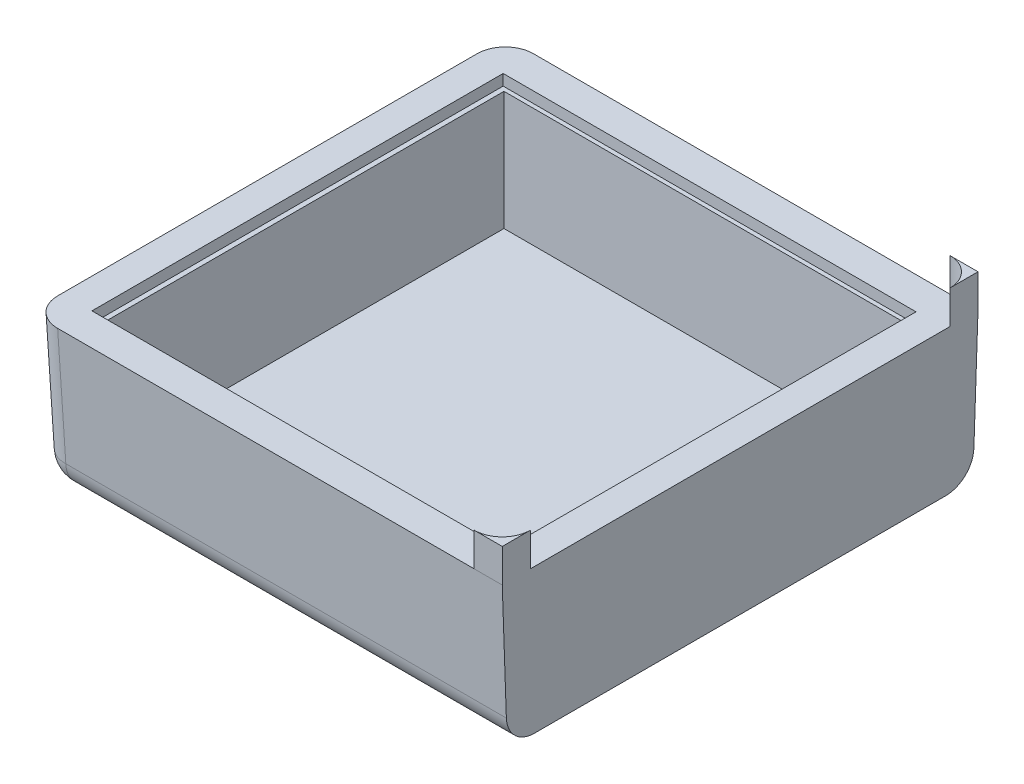
SolidWorks part; units mm, degrees
ref_plane "Front Plane" through (0, 0, 0) normal (0, 0, 1) x (1, 0, 0)
ref_plane "Top Plane" through (0, 0, 0) normal (0, 1, 0) x (1, 0, 0)
ref_plane "Right Plane" through (0, 0, 0) normal (1, 0, 0) x (0, 0, -1)
sketch "Sketch1" plane through (0, 0, 0) normal (0, 1, 0) x (1, 0, 0)
  line L1 (-145.25, -146.05) -> (149.75, -146.05)
  line L2 (-145.25, -146.05) -> (-145.25, 146.05)
  line L3 (-145.25, 146.05) -> (149.75, 146.05)
  line L4 (149.75, -146.05) -> (149.75, 146.05)
  point P0 (-145.25, 0)
  point P2 (0, 0)
  point P3 (0, 0)
  point P6 (0, 0)
  point P7 (0, 0)
  point P8 (0, 0)
  dimension "D1" = 145.25
  dimension "D3" = 292.1
  dimension "D5" = 295
extrude "Boss-Extrude1" add sketch "Sketch1" against normal blind 88.69 draft 2
sketch "Sketch3" plane through (0, 0, 0) normal (0, 1, 0) x (1, 0, 0)
  line L1 (-126.75, -126.25) -> (126.75, -126.25)
  line L4 (126.75, 126.25) -> (126.75, -126.25)
  line L9 (-126.75, 126.25) -> (-126.75, -126.25)
  line L183 (-126.75, 126.25) -> (126.75, 126.25)
  point P1 (-126.75, 0)
  point P8 (122.4856, -125.89)
  dimension "D2" = 253.5
  dimension "D3" = 126.75
  dimension "D1" = 252.5
extrude "Cut-Extrude3" cut sketch "Sketch3" against normal blind 6.5 draft 2
sketch "Sketch5" plane through (0, -6.5, 0) normal (0, 1, 0) x (1, 0, 0)
  line L1 (-123.5, -123.5) -> (123.5, -123.5)
  line L2 (-123.5, -123.5) -> (-123.5, 123.5)
  line L3 (-123.5, 123.5) -> (123.5, 123.5)
  line L4 (123.5, -123.5) -> (123.5, 123.5)
  line L5 (-123.5, -123.5) -> (123.5, 123.5) construction
  line L6 (-123.5, 123.5) -> (123.5, -123.5) construction
  point P0 (0, 0)
  dimension "D1" = 247
extrude "Cut-Extrude4" cut sketch "Sketch5" against normal blind 70.5 draft 2
sketch "Sketch6" plane through (0, 0, 0) normal (0, 0, 1) x (1, 0, 0)
  line L0 (149.75, 0) -> (145, 0)
  line L1 (-145.25, 0) -> (149.75, 0) construction
  line L2 (145, 0) -> (145, -88.69)
  line L3 (-142.1529, -88.69) -> (146.6529, -88.69) construction
  line L4 (145, -88.69) -> (146.6529, -88.69)
  line L5 (146.6529, -88.69) -> (149.75, 0)
  dimension "D1" = 4.75
extrude "Cut-Extrude5" cut sketch "Sketch6" against normal through all both and the other way through all
fillet "Fillet2" radius 17.27 5 edges at (1.4236, -88.69, -142.9529) (-143.7014, -44.345, -144.5014) (-142.1529, -88.69, 0) (-143.7014, -44.345, 144.5014) (1.4236, -88.69, 142.9529)
sketch "Sketch7" plane through (0, 0, 0) normal (0, 1, 0) x (1, 0, 0)
  line L0 (-31.4885, 0) -> (69.7112, 0) construction
  line L1 (145, 146.05) -> (-127.9905, 146.05) construction
  line L2 (145, 146.05) -> (145, -146.05) construction
  line L3 (145, 128.78) -> (145, 146.05)
  line L4 (145, 146.05) -> (127.73, 146.05)
  line L5 (145, -146.05) -> (127.73, -146.05)
  line L6 (145, -128.78) -> (145, -146.05)
  arc A0 (127.73, 146.05) -> (145, 128.78) centre (127.73, 128.78) cw
  arc A1 (127.73, -146.05) -> (145, -128.78) centre (127.73, -128.78) ccw
  dimension "D1" = 17.27
extrude "Boss-Extrude2" add sketch "Sketch7" along normal blind 20.53
